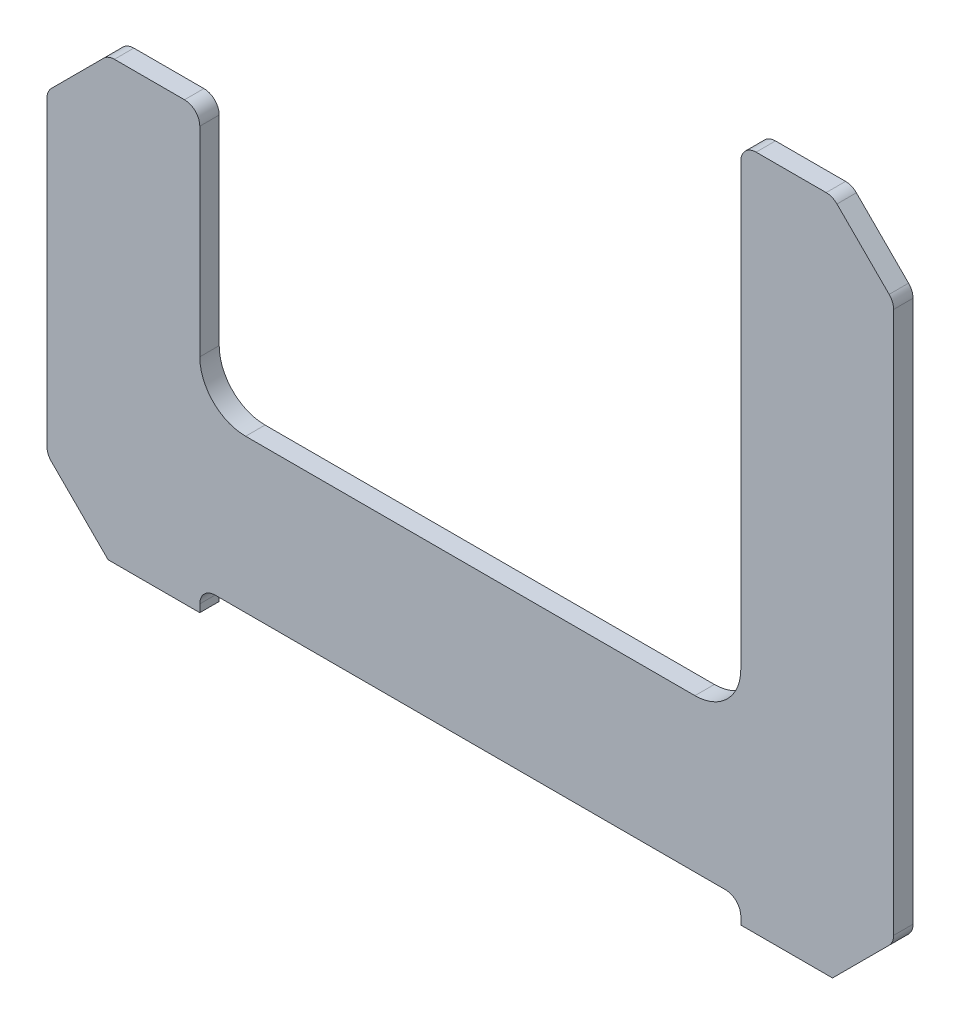
SolidWorks part; units mm, degrees
ref_plane "Front Plane" through (0, 0, 0) normal (0, 0, 1) x (1, 0, 0)
ref_plane "Top Plane" through (0, 0, 0) normal (0, 1, 0) x (1, 0, 0)
ref_plane "Right Plane" through (0, 0, 0) normal (1, 0, 0) x (0, 0, -1)
sketch "Sketch2" plane through (0, 0, 0) normal (0, 0, 1) x (1, 0, 0)
  line L0 (-138.5, 85.3385) -> (-88.5, 85.3385)
  line L1 (-88.5, 85.3385) -> (-88.5, 0)
  line L2 (-88.5, 0) -> (88.5, 0)
  line L3 (88.5, 0) -> (88.5, 164)
  line L4 (88.5, 164) -> (138.5, 164)
  line L5 (138.5, 164) -> (138.5, -57.5)
  line L6 (138.5, -57.5) -> (88.5, -57.5)
  line L7 (88.5, -57.5) -> (88.5, -50)
  line L8 (88.5, -50) -> (-88.5, -50)
  line L9 (-88.5, -50) -> (-88.5, -57.5)
  line L10 (-88.5, -57.5) -> (-138.5, -57.5)
  line L11 (-138.5, -57.5) -> (-138.5, 85.3385)
  line L12 (-33.5, 0) -> (-33.5, 124) construction
  point P10 (-33.5, 0)
  point P14 (88.5, 124)
  point P15 (-33.5, 85.3385)
  dimension "D1" = 124
  dimension "D2" = 122
  dimension "D3" = 55
  dimension "D4" = 40
  dimension "D5" = 50
  dimension "D6" = 50
  dimension "D7" = 7.5
extrude "Boss-Extrude1" add sketch "Sketch2" along normal blind 3.175 and the other way blind 3.175
chamfer "Chamfer1" distance 20 angle 45 4 edges at (-138.5, -57.5, 0) (138.5, -57.5, 0) (138.5, 164, 0) (-138.5, 85.3385, 0)
fillet "Fillet1" radius 15 2 edges at (88.5, 0, 0) (-88.5, 0, 0)
fillet "Fillet2" radius 5 10 edges at (138.5, -37.5, 0) (88.5, -50, 0) (-88.5, -50, 0) (-138.5, -37.5, 0) (-138.5, 65.3385, 0) (-118.5, 85.3385, 0) (-88.5, 85.3385, 0) (138.5, 144, 0) (118.5, 164, 0) (88.5, 164, 0)
sketch "Sketch3" plane through (0, 0, 3.175) normal (0, 0, 1) x (1, 0, 0)
  line L0 (-94.6381, 69.9757) -> (-94.6381, 14.7992)
  line L1 (-94.6381, 14.7992) -> (-97.8131, 14.7992)
  line L2 (-97.8131, 14.7992) -> (-97.8131, 69.9757)
  line L3 (-97.8131, 69.9757) -> (-94.6381, 69.9757)
  line L4 (-127.4635, 65.4691) -> (-114.3536, 78.579)
  line L5 (-114.3536, 78.579) -> (-112.1085, 76.3339)
  line L6 (-112.1085, 76.3339) -> (-125.2184, 63.2241)
  line L7 (-125.2184, 63.2241) -> (-127.4635, 65.4691)
  line L8 (-129.3392, 54.7846) -> (-126.1642, 54.7846)
  line L9 (-126.1642, 54.7846) -> (-126.1642, -28.3138)
  line L10 (-126.1642, -28.3138) -> (-129.3392, -28.3138)
  line L11 (-129.3392, -28.3138) -> (-129.3392, 54.7846)
  line L12 (-127.4635, -37.1329) -> (-125.2184, -34.8879)
  line L13 (-125.2184, -34.8879) -> (-110.9382, -49.1681)
  line L14 (-110.9382, -49.1681) -> (-113.1832, -51.4132)
  line L15 (-113.1832, -51.4132) -> (-127.4635, -37.1329)
  line L16 (-67.7784, -44.3183) -> (-67.7784, -41.1433)
  line L17 (-67.7784, -41.1433) -> (53.0181, -41.1433)
  line L18 (53.0181, -41.1433) -> (53.0181, -44.3183)
  line L19 (53.0181, -44.3183) -> (-67.7784, -44.3183)
  line L20 (114.9313, -49.5303) -> (117.1763, -51.7753)
  line L21 (117.1763, -51.7753) -> (131.7883, -37.1634)
  line L22 (131.7883, -37.1634) -> (129.5432, -34.9183)
  line L23 (129.5432, -34.9183) -> (114.9313, -49.5303)
  line L24 (-67.7784, -4.1746) -> (-67.7784, -7.3496)
  line L25 (-67.7784, -7.3496) -> (63.5847, -7.3496)
  line L26 (63.5847, -7.3496) -> (63.5847, -4.1746)
  line L27 (63.5847, -4.1746) -> (-67.7784, -4.1746)
  line L28 (92.7516, 20.9162) -> (91.2159, 151.9937)
  line L29 (91.2159, 151.9937) -> (94.3909, 151.9937)
  line L30 (94.3909, 151.9937) -> (95.9266, 20.9162)
  line L31 (95.9266, 20.9162) -> (92.7516, 20.9162)
  line L32 (96.8341, 161.8762) -> (96.8341, 158.7012)
  line L33 (96.8341, 158.7012) -> (112.5649, 158.7012)
  line L34 (112.5649, 158.7012) -> (112.5649, 161.8762)
  line L35 (112.5649, 161.8762) -> (96.8341, 161.8762)
  line L37 (117.7781, 156.4535) -> (120.0231, 158.6985)
  line L38 (120.0231, 158.6985) -> (133.8694, 144.8523)
  line L39 (133.8694, 144.8523) -> (131.6243, 142.6072)
  line L40 (131.6243, 142.6072) -> (117.7781, 156.4535)
  line L41 (129.9213, 134.1701) -> (133.0963, 134.1701)
  line L42 (133.0963, 134.1701) -> (133.0963, -24.961)
  line L43 (133.0963, -24.961) -> (129.9213, -24.961)
  line L44 (129.9213, -24.961) -> (129.9213, 134.1701)
  line L45 (118.5, -57.5) -> (137.0355, -38.9645) construction
  line L46 (-137.0355, -38.9645) -> (-118.5, -57.5) construction
  line L47 (-119.9645, 83.874) -> (-137.0355, 66.8029) construction
  line L48 (137.0355, 145.4645) -> (119.9645, 162.5355) construction
  dimension "D1" = 3.175
extrude "Cut-Extrude1" [suppressed] cut sketch "Sketch3" against normal through all
sketch "magnets" plane through (0, 0, 3.175) normal (0, 0, 1) x (1, 0, 0)
  point P0 (94.6751, 158.4052)
  point P1 (114.7572, -50)
  point P2 (131.9288, 140.6094)
  point P3 (131.9288, -32.8111)
  point P4 (0, -44.1618)
  point P5 (-114.0039, -50)
  point P6 (-130.8821, -32.8111)
  point P9 (-130.8821, 62.3605)
  point P10 (-93.5499, 79.7316)
  point P12 (0, -4.7392)
sketch "Sketch4" plane through (0, 0, 3.175) normal (0, 0, 1) x (1, 0, 0)
  line L0 (99.9645, 164) -> (99.9645, 160.825)
  line L1 (116.4289, 164) -> (93.5, 164) construction
  line L2 (99.9645, 160.825) -> (109.9645, 160.825)
  line L3 (109.9645, 160.825) -> (109.9645, 164)
  line L4 (124.9645, 157.5355) -> (122.7194, 155.2905)
  line L5 (137.0355, 145.4645) -> (119.9645, 162.5355) construction
  line L6 (122.7194, 155.2905) -> (129.7905, 148.2194)
  line L7 (129.7905, 148.2194) -> (132.0355, 150.4645)
  line L8 (88.5, 137) -> (91.675, 137)
  line L9 (88.5, 159) -> (88.5, 15) construction
  line L10 (91.675, 137) -> (91.675, 37)
  line L11 (91.675, 37) -> (88.5, 37)
  line L12 (138.5, 103.25) -> (135.325, 103.25)
  line L13 (138.5, -35.4289) -> (138.5, 141.9289) construction
  line L14 (135.325, 103.25) -> (135.325, 3.25)
  line L15 (135.325, 3.25) -> (138.5, 3.25)
  line L16 (-50, 0) -> (-50, -3.175)
  line L17 (73.5, 0) -> (-73.5, 0) construction
  line L18 (-50, -3.175) -> (50, -3.175)
  line L19 (50, -3.175) -> (50, 0)
  line L20 (-50, -50) -> (-50, -46.825)
  line L21 (-83.5, -50) -> (83.5, -50) construction
  line L22 (-50, -46.825) -> (50, -46.825)
  line L23 (50, -46.825) -> (50, -50)
  line L24 (-135.325, -6.0808) -> (-138.5, -6.0808)
  line L25 (-138.5, 63.2674) -> (-138.5, -35.4289) construction
  line L26 (-135.325, 33.9192) -> (-135.325, -6.0808)
  line L27 (-135.325, 33.9192) -> (-138.5, 33.9192)
  line L28 (-132.0355, 71.8029) -> (-129.7905, 69.5579)
  line L29 (-119.9645, 83.874) -> (-137.0355, 66.8029) construction
  line L30 (-129.7905, 69.5579) -> (-122.7194, 76.6289)
  line L31 (-122.7194, 76.6289) -> (-124.9645, 78.874)
  line L32 (-109.9645, 85.3385) -> (-109.9645, 82.1635)
  line L33 (-93.5, 85.3385) -> (-116.4289, 85.3385) construction
  line L35 (-109.9645, 82.1635) -> (-99.9645, 82.1635)
  line L36 (-88.5, 67.6692) -> (-91.675, 67.6692)
  line L37 (-88.5, 15) -> (-88.5, 80.3385) construction
  line L38 (-91.675, 67.6692) -> (-91.675, 27.6692)
  line L39 (-91.675, 27.6692) -> (-88.5, 27.6692)
  line L40 (-107.375, -57.5) -> (-107.375, -54.325)
  line L41 (-118.5, -57.5) -> (-88.5, -57.5) construction
  line L42 (-107.375, -54.325) -> (-97.375, -54.325)
  line L43 (-97.375, -54.325) -> (-97.375, -57.5)
  line L44 (97.375, -57.5) -> (97.375, -54.325)
  line L45 (88.5, -57.5) -> (118.5, -57.5) construction
  line L46 (97.375, -54.325) -> (107.375, -54.325)
  line L47 (107.375, -54.325) -> (107.375, -57.5)
  line L48 (-132.0988, -43.9012) -> (-129.8537, -41.6561)
  line L49 (-137.0355, -38.9645) -> (-118.5, -57.5) construction
  line L50 (-129.8537, -41.6561) -> (-122.7827, -48.7272)
  line L51 (-122.7827, -48.7272) -> (-125.0277, -50.9723)
  line L52 (125.0277, -50.9723) -> (122.7827, -48.7272)
  line L53 (118.5, -57.5) -> (137.0355, -38.9645) construction
  line L54 (122.7827, -48.7272) -> (129.8537, -41.6561)
  line L55 (129.8537, -41.6561) -> (132.0988, -43.9012)
  line L56 (-128.5633, -47.4367) -> (-126.3182, -45.1917) construction
  line L57 (-102.375, -57.5) -> (-102.375, -54.325)
  line L58 (102.375, -57.5) -> (102.375, -54.325)
  line L59 (-128.5, 75.3385) -> (-126.2549, 73.0934) construction
  line L60 (-104.9645, 82.1635) -> (-104.9645, 85.3385) construction
  line L61 (126.2549, 151.7549) -> (128.5, 154) construction
  line L62 (126.3182, -45.1917) -> (128.5633, -47.4367) construction
  line L63 (88.5, -57.5) -> (116.25, -57.5) construction
  line L64 (120.091, -55.909) -> (137.0355, -38.9645) construction
  line L65 (120.091, -55.909) -> (118.5, -57.5) construction
  line L66 (118.5, -57.5) -> (116.25, -57.5) construction
  line L67 (-88.5, -57.5) -> (-116.25, -57.5) construction
  line L68 (-116.25, -57.5) -> (-118.5, -57.5) construction
  line L69 (-118.5, -57.5) -> (-120.091, -55.909) construction
  line L70 (-120.091, -55.909) -> (-137.0355, -38.9645) construction
  line L71 (-99.9645, 82.1635) -> (-99.9645, 85.3385)
  point P95 (0, -46.825)
  point P97 (0, -50)
  point P99 (0, -3.175)
  point P101 (135.325, 53.25)
  point P103 (138.5, 53.25)
  point P104 (91.675, 87)
  point P105 (88.5, 87)
  point P106 (104.9645, 160.825)
  point P107 (104.9645, 164)
  point P108 (128.5, 154)
  point P109 (126.2549, 151.7549)
  point P112 (-135.325, 13.9192)
  point P113 (-138.5, 13.9192)
  point P114 (-91.675, 47.6692)
  point P115 (-88.5, 47.6692)
  point P116 (126.3182, -45.1917)
  point P117 (127.7678, -48.2322)
  line M1 (118.5, -57.5) -> (137.0355, -38.9645)
  line M3 (138.5, -35.4289) -> (138.5, 141.9289)
  line M5 (137.0355, 145.4645) -> (119.9645, 162.5355)
  line M7 (116.4289, 164) -> (93.5, 164)
  line M9 (88.5, 159) -> (88.5, 15)
  line M11 (73.5, 0) -> (-73.5, 0)
  line M13 (-88.5, 15) -> (-88.5, 80.3385)
  line M15 (-93.5, 85.3385) -> (-116.4289, 85.3385)
  line M17 (-119.9645, 83.874) -> (-137.0355, 66.8029)
  line M19 (-138.5, 63.2674) -> (-138.5, -35.4289)
  line M21 (-137.0355, -38.9645) -> (-118.5, -57.5)
  line M22 (-118.5, -57.5) -> (-88.5, -57.5)
  line M25 (-83.5, -50) -> (83.5, -50)
  line M28 (88.5, -57.5) -> (118.5, -57.5)
  dimension "D1" = 3.175
  dimension "D5" = 100
  dimension "D6" = 100
  dimension "D7" = 100
  dimension "D8" = 100
  dimension "D4" = 10
  dimension "D2" = 10
  dimension "D10" = 2.25
  dimension "D3" = 2.25
  dimension "D11" = 10
  dimension "D13" = 3.175
  dimension "D12" = 10
  dimension "D14" = 10
  dimension "D15" = 10
  dimension "D16" = 10
  dimension "D17" = 10
  dimension "D18" = 40
  dimension "D19" = 3.175
extrude "wall_slots" [suppressed] cut sketch "Sketch4" against normal blind 60 contours L26 L27 L24 M19 | L18 L19 L16 M11 | L23 L22 L20 M25 | L51 L50 L48 M21 | L57 L43 L42 M22 | L57 L42 L40 M22 | L38 L39 L36 M13 | L35 L71 L32 M15 | L30 L31 L28 M17 | L58 L47 L46 M28 | L58 L46 L44 M28 | L55 L54 L52 M1 | L14 L15 L12 M3 | L11 L10 L8 M9 | L2 L3 L0 M7 | L6 L7 L4 M5
sketch "wall_measure" [suppressed] plane through (0, 0, 3.175) normal (0, 0, 1) x (1, 0, 0)
  line L0 (-116.4289, 85.3385) -> (-116.4289, 82.1635)
  line L1 (-116.4289, 82.1635) -> (-93.5, 82.1635)
  line L2 (-93.5, 82.1635) -> (-93.5, 85.3385)
  line L4 (93.5, 164) -> (93.5, 160.825)
  line L5 (93.5, 160.825) -> (116.4289, 160.825)
  line L6 (116.4289, 160.825) -> (116.4289, 164)
  line L7 (99.9645, 160.825) -> (109.9645, 160.825) construction
  line L8 (119.9645, 162.5355) -> (117.7194, 160.2905)
  line L9 (117.7194, 160.2905) -> (134.7905, 143.2194)
  line L10 (134.7905, 143.2194) -> (137.0355, 145.4645)
  line L11 (137.0355, 145.4645) -> (132.0355, 150.4645) construction
  line L12 (88.5, 159) -> (91.675, 159)
  line L13 (91.675, 159) -> (91.675, 15)
  line L14 (91.675, 15) -> (88.5, 15)
  line L15 (88.5, 37) -> (88.5, 15) construction
  line L16 (138.5, 141.9289) -> (135.325, 141.9289)
  line L17 (135.325, 141.9289) -> (135.325, -35.4289)
  line L18 (135.325, -35.4289) -> (138.5, -35.4289)
  line L19 (-73.5, 0) -> (-73.5, -3.175)
  line L20 (-73.5, -3.175) -> (73.5, -3.175)
  line L21 (73.5, -3.175) -> (73.5, 0)
  line L22 (-83.5, -50) -> (-83.5, -46.825)
  line L23 (-83.5, -46.825) -> (83.5, -46.825)
  line L24 (83.5, -46.825) -> (83.5, -50)
  line L25 (88.5, -55) -> (116.2868, -55)
  line L26 (116.2868, -55) -> (116.2868, -57.5)
  line L27 (137.0355, -38.9645) -> (134.7905, -36.7194)
  line L28 (134.7905, -36.7194) -> (117.8199, -53.69)
  line L29 (117.8199, -53.69) -> (120.065, -55.935)
  line L30 (118.5, -57.5) -> (125.0277, -50.9723) construction
  line L31 (122.7827, -48.7272) -> (129.8537, -41.6561) construction
  line L32 (116.2868, -57.5) -> (118.5, -57.5) construction
  line L33 (118.5, -57.5) -> (120.065, -55.935) construction
  line L34 (-138.5, 63.2674) -> (-133.5, 63.2674)
  line L35 (-133.5, 63.2674) -> (-133.5, -35.4289)
  line L36 (-133.5, -35.4289) -> (-138.5, -35.4289)
  line L37 (-88.5, 80.3385) -> (-91.675, 80.3385)
  line L38 (-91.675, 80.3385) -> (-91.675, 15)
  line L39 (-91.675, 15) -> (-88.5, 15)
  line L40 (-50, -46.825) -> (50, -46.825) construction
  line L41 (-50, -3.175) -> (50, -3.175) construction
  line L42 (135.325, 103.25) -> (135.325, 3.25) construction
  line L43 (91.675, 137) -> (91.675, 37) construction
  line L44 (122.7194, 155.2905) -> (129.7905, 148.2194) construction
  line L45 (-91.675, 67.6692) -> (-91.675, 27.6692) construction
  line L47 (-109.9645, 82.1635) -> (-99.9645, 82.1635) construction
  arc A0 (73.5, 0) -> (88.5, 15) centre (73.5, 15) ccw construction
  arc A1 (-88.5, 15) -> (-73.5, 0) centre (-73.5, 15) ccw construction
  dimension "D1" = 22.9289
  dimension "D2" = 22.9289
  dimension "D3" = 24.1421
  dimension "D4" = 144
  dimension "D5" = 177.3579
  dimension "D6" = 147
  dimension "D7" = 167
  dimension "D8" = 24
  dimension "D9" = 2.2132
  dimension "D10" = 27.7868
  dimension "D11" = 98.6963
  dimension "D12" = 65.3385
equation "\"dX\"= 122mm"
equation "\"dY\"= 124mm"
equation "\"hmotor\"= 50mm"
equation "\"D1@Sketch2\"=\"dY\""
equation "\"D2@Sketch2\"=\"dX\""
equation "\"D5@Sketch2\"=\"hmotor\""
equation "\"D6@Sketch2\"=\"hmotor\""
equation "\"t_wood\"= 0.25in"
equation "\"D1@Boss-Extrude1\"=\"t_wood\"/2"
equation "\"D2@Boss-Extrude1\"=\"t_wood\"/2"
equation "\"D1@Sketch3\"=\"t_wood\"/2"
equation "\"D1@Sketch4\"=\"t_wood\"/2"
equation "\"D13@Sketch4\"=\"t_wood\"/2"
equation "\"D19@Sketch4\"=\"t_wood\"/2"
